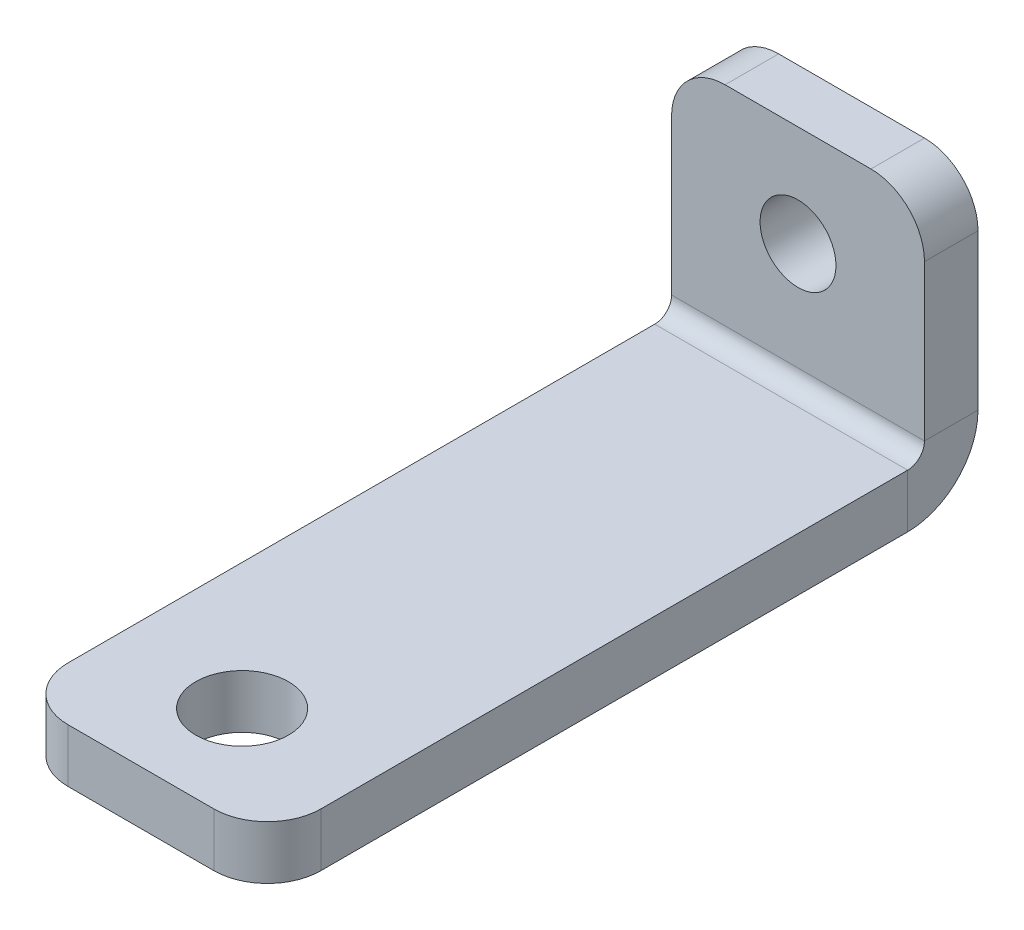
SolidWorks part; units mm, degrees
note: The reader was unsure of these and kept them because the rebuilt part matched: thickness of "Base-Flange1", "Edge-Flange1", "Sheet-Metal1", "Sheet-Metal2", "Sheet-Metal3", "Sheet-Metal4"; flange length of "Edge-Flange1".
material "3003-H14"
ref_plane "Front Plane" through (0, 0, 0) normal (0, 0, 1) x (1, 0, 0)
ref_plane "Top Plane" through (0, 0, 0) normal (0, 1, 0) x (1, 0, 0)
ref_plane "Right Plane" through (0, 0, 0) normal (1, 0, 0) x (0, 0, -1)
sketch "Sketch1" plane through (0, 0, 0) normal (0, 1, 0) x (1, 0, 0)
  line L1 (-7.5, -21.075) -> (7.5, -21.075)
  line L2 (-7.5, -21.075) -> (-7.5, 21.075)
  line L3 (-7.5, 21.075) -> (7.5, 21.075)
  line L4 (7.5, -21.075) -> (7.5, 21.075)
  line L5 (-7.5, -21.075) -> (7.5, 21.075) construction
  line L6 (-7.5, 21.075) -> (7.5, -21.075) construction
  point P0 (0, 0)
  dimension "D1" = 42.15
  dimension "D2" = 15
base flange "Base-Flange1" sketch "Sketch1" thickness 3.175 reverse thickness direction yes parameters "D1"=0.7366
edge flange "Edge-Flange1" sketch "Sketch8" flange angle 90 flange length 16.56 flange position material inside bend radius 1 thickness 3.175 relief rectangular parameters "D6"=10
sketch "Sketch8" plane through (0, 3.175, -21.075) normal (0, 0, -1) x (-1, 0, 0)
  line L2 (-7.5, 0) -> (-7.5, 13.385)
  line L3 (-7.5, 13.385) -> (7.5, 13.385)
  line L4 (7.5, 13.385) -> (7.5, 0)
  line L7 (-7.5, 0) -> (7.5, 0) construction
  line L8 (-7.5, 0) -> (7.5, 0)
bend "EdgeBend1" bend radius 1 bend angle 90 parameters "D5"=1
hole_wizard "M5 Clearance Hole1" positions "Sketch9" profile "Sketch10" hole size "M5" standard "ANSI Metric" end condition through all
sketch "Sketch9" plane through (0, 3.175, 0) normal (0, 1, 0) x (1, 0, 0)
  line L0 (-7.5, -21.075) -> (7.5, -21.075) construction
  line L1 (-7.5, 16.9) -> (-7.5, -21.075) construction
  point P0 (0, -15.075)
  dimension "D1" = 6
  dimension "D2" = 7.5
sketch "Sketch10" plane through (0, 3.175, 15.075) normal (1, 0, 0) x (0, 0, 1)
  line L0 (0, 0) -> (0, 3.175)
  line L1 (0, 3.175) -> (2.75, 3.175)
  line L2 (2.75, 3.175) -> (2.75, 0)
  line L5 (2.75, 0) -> (0, 0)
  line L11 (0, -6.35) -> (0, 107.95) construction
  dimension "Thru Hole Dia." = 5.5
  dimension "Thru Hole Depth" = 3.175
hole_wizard "M4 Clearance Hole1" positions "Sketch11" profile "Sketch12" hole size "M4" standard "ANSI Metric" end condition through all
sketch "Sketch11" plane through (0, 0, -17.9) normal (0, 0, 1) x (1, 0, 0)
  line L0 (-7.5, 16.56) -> (7.5, 16.56) construction
  point P0 (0, 10.56)
  dimension "D1" = 6
sketch "Sketch12" plane through (0, 10.56, -17.9) normal (1, 0, 0) x (0, -1, 0)
  line L0 (0, 0) -> (0, 3.175)
  line L1 (0, 3.175) -> (2.25, 3.175)
  line L2 (2.25, 3.175) -> (2.25, 0)
  line L5 (2.25, 0) -> (0, 0)
  line L11 (0, -6.35) -> (0, 107.95) construction
  dimension "Thru Hole Dia." = 4.5
  dimension "Thru Hole Depth" = 3.175
fillet "Fillet1" radius 3.175 4 edges at (-7.5, 16.56, -19.4875) (7.5, 16.56, -19.4875) (-7.5, 1.5875, 21.075) (7.5, 1.5875, 21.075)
sketch "Bend-Lines1" [suppressed] plane through (0, 0, 0) normal (0, 1, 0) x (1, 0, 0)
sketch "Bounding-Box1" [suppressed] plane through (0, 0, 0) normal (0, 1, 0) x (1, 0, 0)
sheet metal parameters "Sheet-Metal1" thickness 3.175 parameters "D1"=0.7366
flat pattern "Flat-Pattern1" [suppressed]
sketch "Bend-Lines2" plane through (0, 0, 0) normal (0, 1, 0) x (1, 0, 0)
sketch3d "Bounding-Box2" [suppressed]
  line L0 (-8, -16, 0) -> (-8, 16, 0) construction
  line L1 (8, -16, 0) -> (8, 16, 0) construction
  line L2 (-8, -16, 0) -> (8, -16, 0) construction
  line L3 (-8, 16, 0) -> (8, 16, 0) construction
sheet metal parameters "Sheet-Metal2" thickness 3.175 parameters "D1"=0.7366, "D7"=3.18
flat pattern "Flat-Pattern1"
sketch "Bend-Lines2" plane through (0, 0, 0) normal (0, -1, 0) x (-1, 0, 0)
  line L0 (7.5, 12.9107) -> (-7.5, 12.9107) construction
  line L1 (7.5, 12.9107) -> (-7.5, 12.9107) construction
sketch3d "Bounding-Box2" [suppressed]
  line L0 (7.5, -15, 0) -> (7.5, 26.8214, 0) construction
  line L1 (-7.5, -15, 0) -> (-7.5, 26.8214, 0) construction
  line L2 (7.5, -15, 0) -> (-7.5, -15, 0) construction
  line L3 (7.5, 26.8214, 0) -> (-7.5, 26.8214, 0) construction
bend of the flat pattern "Flatten-<EdgeBend1>1"
sheet metal parameters "Sheet-Metal3" thickness 3.175 parameters "D1"=0.7366, "D7"=3.18
flat pattern "Flat-Pattern1"
sketch "Bend-Lines2" plane through (0, 0, 0) normal (0, -1, 0) x (-1, 0, 0)
  line L0 (7.5, 12.9107) -> (-7.5, 12.9107) construction
  line L1 (7.5, 12.9107) -> (-7.5, 12.9107) construction
sketch3d "Bounding-Box2" [suppressed]
  line L0 (7.5, -15, 0) -> (7.5, 26.8214, 0) construction
  line L1 (-7.5, -15, 0) -> (-7.5, 26.8214, 0) construction
  line L2 (7.5, -15, 0) -> (-7.5, -15, 0) construction
  line L3 (7.5, 26.8214, 0) -> (-7.5, 26.8214, 0) construction
bend of the flat pattern "Flatten-<EdgeBend1>1"
sheet metal parameters "Sheet-Metal4" thickness 3.175 parameters "D1"=0.7366, "D7"=3.18
flat pattern "Flat-Pattern1"
sketch "Bend-Lines2" plane through (0, 0, 0) normal (0, -1, 0) x (-1, 0, 0)
  line L0 (7.5, 18.9322) -> (-7.5, 18.9322) construction
  line L1 (7.5, 18.9322) -> (-7.5, 18.9322) construction
sketch3d "Bounding-Box2" [suppressed]
  line L0 (-7.5001, -21.075, 0) -> (-7.5, 33.3494, 0) construction
  line L1 (7.4999, -21.075, 0) -> (7.5, 33.3494, 0) construction
  line L2 (-7.5001, -21.075, 0) -> (7.4999, -21.075, 0) construction
  line L3 (-7.5, 33.3494, 0) -> (7.5, 33.3494, 0) construction
bend of the flat pattern "Flatten-<EdgeBend1>1"
